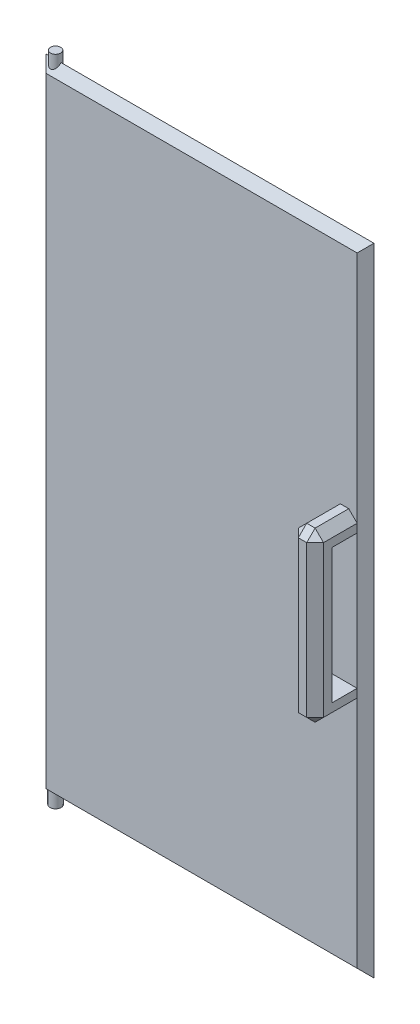
SolidWorks part; units mm, degrees
ref_plane "Front Plane" through (0, 0, 0) normal (0, 0, 1) x (1, 0, 0)
ref_plane "Top Plane" through (0, 0, 0) normal (0, 1, 0) x (1, 0, 0)
ref_plane "Right Plane" through (0, 0, 0) normal (1, 0, 0) x (0, 0, -1)
sketch "Sketch1" plane through (0, 0, 0) normal (0, 0, 1) x (1, 0, 0)
  line L0 (-40.5907, 32.0721) -> (349.4093, 32.0721)
  line L1 (349.4093, 32.0721) -> (349.4093, -724.7279)
  line L2 (349.4093, -724.7279) -> (-40.5907, -724.7279)
  line L3 (-40.5907, -724.7279) -> (-40.5907, 32.0721)
extrude "Boss-Extrude1" add sketch "Sketch1" along normal blind 20
sketch "Sketch2" plane through (0, 32.0721, 0) normal (0, 1, 0) x (1, 0, 0)
  circle A0 centre (-28.7838, -10.4351) radius 6.05
extrude "Boss-Extrude2" add sketch "Sketch2" along normal blind 10
sketch "Sketch3" plane through (0, -724.7279, 0) normal (0, -1, 0) x (1, 0, 0)
  circle A0 centre (-28.7838, 10.4351) radius 6.631
extrude "Boss-Extrude3" add sketch "Sketch3" along normal blind 10
chamfer "Chamfer1" distance 10 angle 45 8 edges at (-40.5907, -346.3279, 20) (154.4093, -724.7279, 20) (349.4093, -346.3279, 20) (154.4093, 32.0721, 20) (-40.5907, -346.3279, 0) (154.4093, -724.7279, 0) (349.4093, -346.3279, 0) (154.4093, 32.0721, 0)
sketch "Sketch4" plane through (0, 0, 20) normal (0, 0, 1) x (1, 0, 0)
  line L0 (339.4093, 22.0721) -> (339.4093, -346.3279)
  line L1 (339.4093, -714.7279) -> (339.4093, 22.0721) construction
  line L3 (309.4093, -346.3279) -> (309.4093, -246.3279)
  line L4 (309.4093, -246.3279) -> (339.4093, -246.3279)
  line L5 (339.4093, -246.3279) -> (339.4093, -446.3279)
  line L6 (339.4093, -446.3279) -> (309.4093, -446.3279)
  line L7 (309.4093, -446.3279) -> (309.4093, -346.3279)
extrude "Boss-Extrude5" add sketch "Sketch4" along normal blind 50 contours L7 L6 L4 L3 region at (324.4093, -346.3279, 20)
sketch "Sketch5" plane through (339.4093, 0, 0) normal (1, 0, 0) x (0, 0, -1)
  line L0 (-20, -246.3279) -> (-20, -266.3279)
  line L1 (-20, -446.3279) -> (-20, -246.3279) construction
  line L2 (-20, -266.3279) -> (-50, -266.3279)
  line L3 (-50, -266.3279) -> (-50, -426.3279)
  line L4 (-50, -426.3279) -> (-20, -426.3279)
  line L5 (-20, -426.3279) -> (-20, -266.3279)
  line M1 (-20, -446.3279) -> (-20, -246.3279)
extrude "Cut-Extrude1" cut sketch "Sketch5" against normal blind 50 contours L3 L4 L2 M1 region at (339.4093, -346.3279, 35)
chamfer "Chamfer2" distance 10 angle 45 8 edges at (324.4093, -246.3279, 70) (339.4093, -246.3279, 45) (339.4093, -346.3279, 70) (339.4093, -446.3279, 45) (324.4093, -446.3279, 70) (309.4093, -446.3279, 45) (309.4093, -346.3279, 70) (309.4093, -246.3279, 45)
